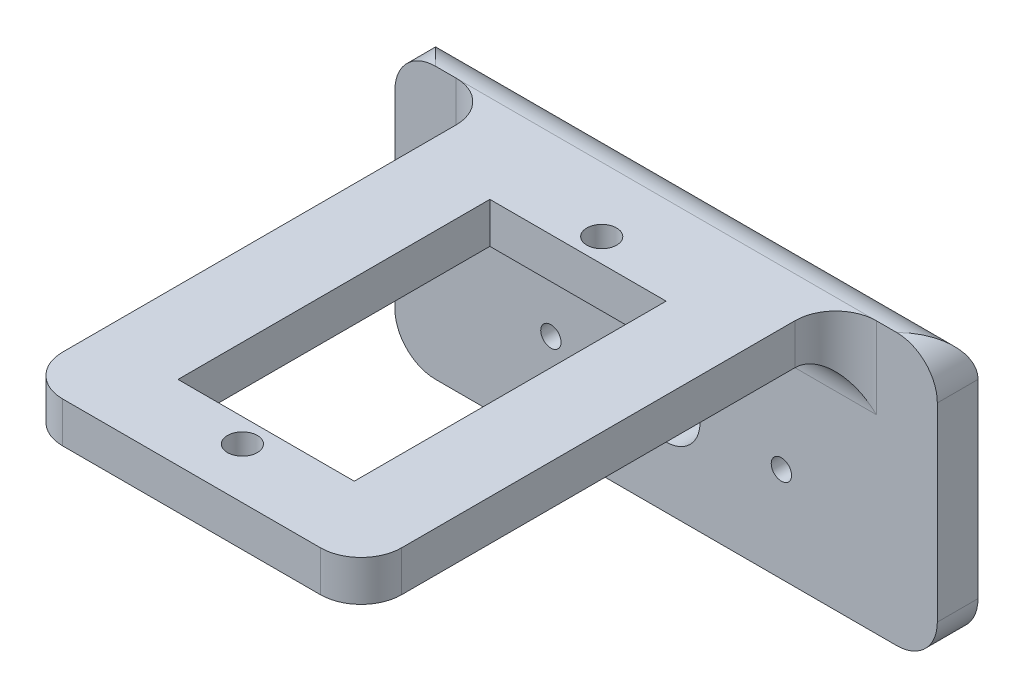
SolidWorks part; units mm, degrees
ref_plane "Plano frontal" through (0, 0, 0) normal (0, 0, 1) x (1, 0, 0)
ref_plane "Plano superior" through (0, 0, 0) normal (0, 1, 0) x (1, 0, 0)
ref_plane "Plano direito" through (0, 0, 0) normal (1, 0, 0) x (0, 0, -1)
sketch "Esboço1" plane through (0, 0, 0) normal (0, 0, 1) x (1, 0, 0)
  line L13 (-20, -12) -> (20, -12)
  line L14 (-20, -12) -> (-20, 8)
  line L15 (-20, 8) -> (20, 8)
  line L16 (20, -12) -> (20, 8)
  arc A12 (-2.4269, 0.6) -> (-2.4269, -0.6) centre (0, 0) ccw
  point P29 (0, 8)
  dimension "D8" = 5
  dimension "D3" = 20
  dimension "D4" = 40
  dimension "D5" = 12
extrude "Ressalto-extrusão1" add sketch "Esboço1" against normal blind 1 contours L13 L16 L15 L14 region at (0, -2, 0)
sketch "Esboço2" plane through (0, 0, 0) normal (0, 0, 1) x (1, 0, 0)
  line L0 (-20, 8) -> (20, 8) construction
  circle A0 centre (0, -5) radius 2.5
  circle A4 centre (-8.5, -5) radius 0.75
  dimension "D1" = 13
  dimension "D2" = 5
  dimension "D3" = 1.5
  dimension "D4" = 8.5
sketch "Esboço3" plane through (0, 0, 0) normal (0, 0, 1) x (1, 0, 0)
  line L1 (-20, -12) -> (20, -12)
  line L2 (-20, -12) -> (-20, 8)
  line L3 (-20, 8) -> (20, 8)
  line L4 (20, -12) -> (20, 8)
extrude "Ressalto-extrusão2" add sketch "Esboço3" along normal blind 2
extrude "Corte-extrusão1" cut sketch "Esboço2" along normal up to surface and the other way up to surface up to face at (0, -2, 2) other way up to face at (0, -2, -1)
sketch "Esboço4" plane through (0, 8, 0) normal (0, 1, 0) x (1, 0, 0)
  line L0 (20, -2) -> (-20, -2) construction
  line L1 (6.5, -31.5) -> (-6.5, -31.5)
  line L2 (6.5, -31.5) -> (6.5, -8.5)
  line L3 (6.5, -8.5) -> (-6.5, -8.5)
  line L4 (-6.5, -31.5) -> (-6.5, -8.5)
  line L5 (-20, 1) -> (20, 1) construction
  line L6 (12.5, -2) -> (-12.5, -2)
  line L7 (12.5, -2) -> (12.5, -37)
  line L8 (12.5, -37) -> (-12.5, -37)
  line L9 (-12.5, -2) -> (-12.5, -37)
  line L10 (-12.5, -2) -> (12.5, -2)
  line L11 (-12.5, -2) -> (-12.5, 1)
  line L12 (-12.5, 1) -> (12.5, 1)
  line L13 (12.5, -2) -> (12.5, 1)
  circle A0 centre (0, -6.75) radius 1.1
  circle A1 centre (0, -33.25) radius 1.1
  point P6 (0, -31.5)
  point P13 (0, -2)
  point P14 (0, -37)
  line M5 (-20, -2) -> (20, -2)
  line M7 (20, 1) -> (-20, 1)
  dimension "D6" = 4.75
  dimension "D7" = 2.2
  dimension "D8" = 26.5
  dimension "D1" = 6.5
  dimension "D2" = 23
  dimension "D3" = 13
  dimension "D4" = 25
  dimension "D5" = 35
extrude "Ressalto-extrusão3" add sketch "Esboço4" against normal blind 3 contours L13 L11 M5 M7 | L9 L8 L7 L1 L4 L3 L2 M5 region at (12.0699, 8, 19.5) region at (0, 8, 0.5)
mirror "Mirror1" about plane through (0, 0, 0) normal (1, 0, 0) of "Corte-extrusão1"
fillet "Fillet2" radius 3 10 edges at (0, 8, -1) (20, 8, 0.5) (20, -12, 0.5) (-20, -12, 0.5) (-20, 8, 0.5) (12.5, 6.5, 37) (-12.5, 6.5, 37) (12.5, 6.5, 2) (0, 5, 2) (-12.5, 6.5, 2)
move or copy body "Body-Move/Copy1" [suppressed] bodies to move or copy 107
